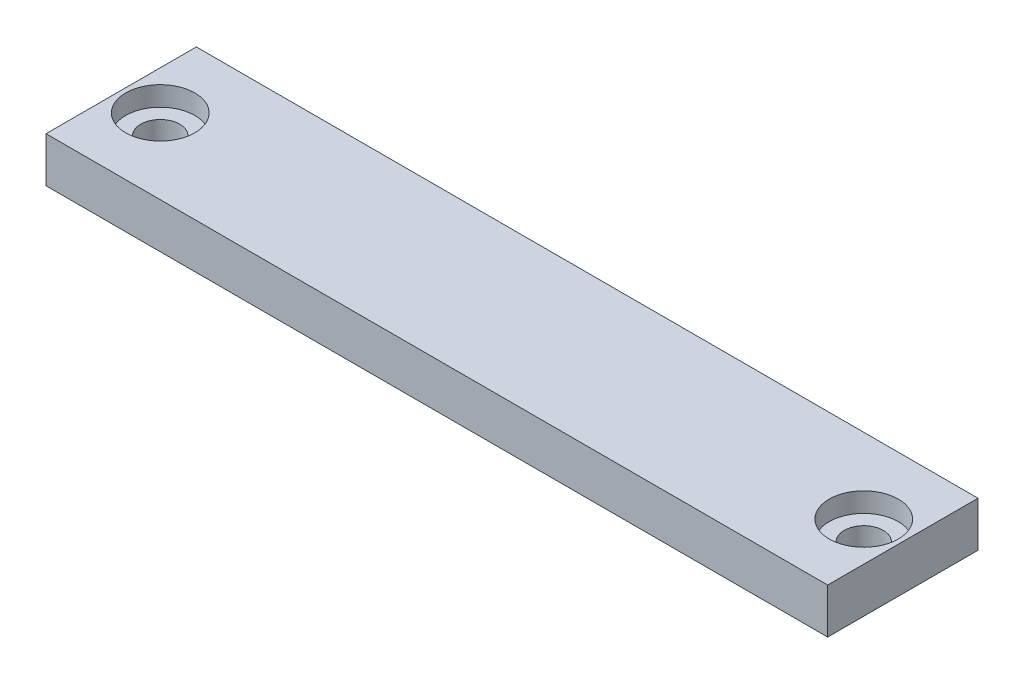
SolidWorks part; units mm, degrees
ref_plane "Front Plane" through (0, 0, 0) normal (0, 0, 1) x (1, 0, 0)
ref_plane "Top Plane" through (0, 0, 0) normal (0, 1, 0) x (1, 0, 0)
ref_plane "Right Plane" through (0, 0, 0) normal (1, 0, 0) x (0, 0, -1)
sketch "Sketch1" plane through (0, 0, 0) normal (0, 0, 1) x (1, 0, 0)
  line L1 (-26, 21.75) -> (26, 21.75)
  line L2 (-26, 21.75) -> (-26, 24.75)
  line L3 (-26, 24.75) -> (26, 24.75)
  line L4 (26, 21.75) -> (26, 24.75)
extrude "Boss-Extrude1" add sketch "Sketch1" along normal blind 10 from offset 40 offset against normal yes
sketch "Sketch2" plane through (0, 0, 0) normal (0, 1, 0) x (1, 0, 0)
  circle A0 centre (-23.4, 35) radius 1.3
extrude "Boss-Extrude2" add sketch "Sketch2" along normal blind 6 from offset 20 separate body
combine bodies "Combine1" operation type subtract main body 101 bodies to subtract 102
sketch "Sketch3" plane through (0, 0, 0) normal (0, 1, 0) x (1, 0, 0)
  circle A0 centre (-23.4, 35) radius 2.3
extrude "Boss-Extrude3" add sketch "Sketch3" along normal blind 2.55 from offset 23.45 separate body
combine bodies "Combine2" operation type subtract main body 103 bodies to subtract 104
sketch "Sketch4" plane through (0, 0, 0) normal (0, 1, 0) x (1, 0, 0)
  circle A0 centre (23.4, 35) radius 1.3
extrude "Boss-Extrude4" add sketch "Sketch4" along normal blind 6 from offset 20 separate body
combine bodies "Combine3" operation type subtract main body 105 bodies to subtract 106
sketch "Sketch5" plane through (0, 0, 0) normal (0, 1, 0) x (1, 0, 0)
  circle A0 centre (23.4, 35) radius 2.3
extrude "Boss-Extrude5" add sketch "Sketch5" along normal blind 2.55 from offset 23.45 separate body
combine bodies "Combine4" operation type subtract main body 107 bodies to subtract 108
